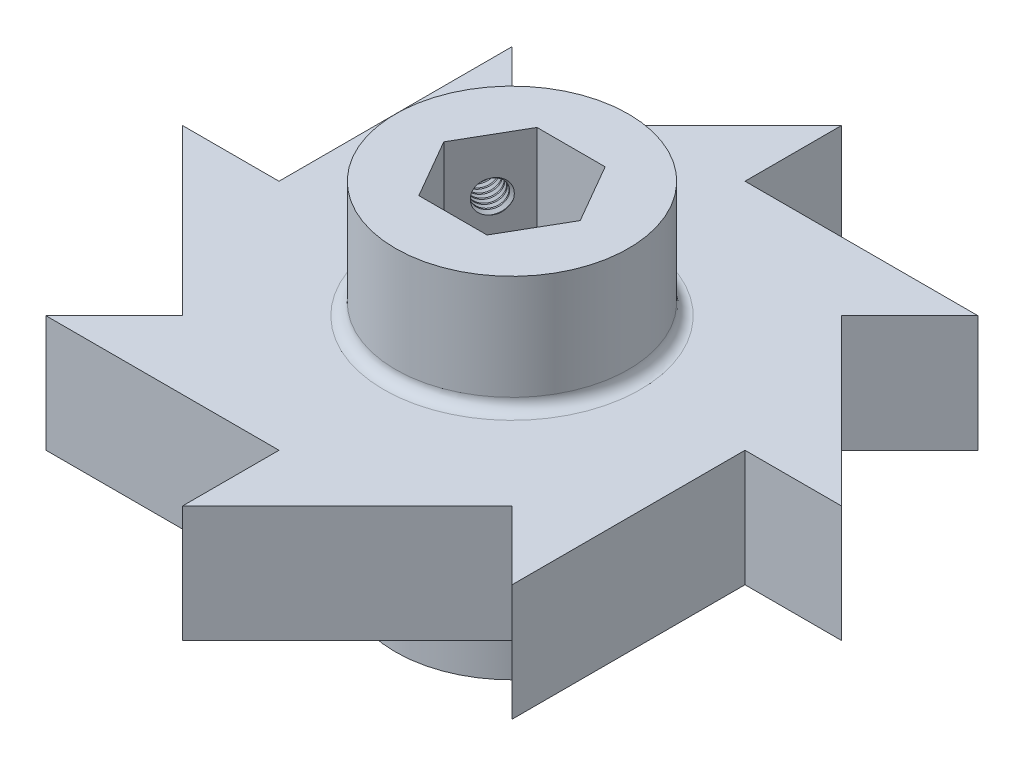
SolidWorks part; units mm, degrees
ref_plane "Front Plane" through (0, 0, 0) normal (0, 0, 1) x (1, 0, 0)
ref_plane "Top Plane" through (0, 0, 0) normal (0, 1, 0) x (1, 0, 0)
ref_plane "Right Plane" through (0, 0, 0) normal (1, 0, 0) x (0, 0, -1)
sketch "Sketch1" plane through (0, 0, 0) normal (0, 1, 0) x (1, 0, 0)
  line L0 (0, 77.6438) -> (0, -76.6604) construction
  line L1 (-67.7775, 0) -> (60.5568, 0) construction
  line L2 (-10.521, 25.4) -> (-17.9605, 17.9605)
  line L3 (-25.4, 10.521) -> (-25.4, 0)
  line L4 (-25.4, -10.521) -> (-17.9605, -17.9605)
  line L5 (-10.521, -25.4) -> (0, -25.4)
  line L6 (10.521, -25.4) -> (17.9605, -17.9605)
  line L7 (25.4, -10.521) -> (25.4, 0)
  line L8 (25.4, 10.521) -> (17.9605, 17.9605)
  line L9 (10.521, 25.4) -> (0, 25.4)
  line L10 (-17.9605, 17.9605) -> (33.7657, -33.7657) construction
  line L11 (17.9605, 17.9605) -> (-25.4, -25.4) construction
  line L12 (-25.4, -10.521) -> (-35.921, 0)
  line L13 (-35.921, 0) -> (-25.4, 0)
  line L15 (-25.4, 10.521) -> (-25.4, 25.4)
  line L16 (-25.4, 25.4) -> (-17.9605, 17.9605)
  line L18 (-10.521, 25.4) -> (0, 35.921)
  line L19 (0, 35.921) -> (0, 25.4)
  line L21 (10.521, 25.4) -> (25.4, 25.4)
  line L22 (25.4, 25.4) -> (17.9605, 17.9605)
  line L24 (25.4, 10.521) -> (35.921, 0)
  line L25 (35.921, 0) -> (25.4, 0)
  line L27 (25.4, -10.521) -> (25.4, -25.4)
  line L28 (25.4, -25.4) -> (17.9605, -17.9605)
  line L30 (10.521, -25.4) -> (0, -35.921)
  line L31 (0, -35.921) -> (0, -25.4)
  line L33 (-10.521, -25.4) -> (-25.4, -25.4)
  line L34 (-25.4, -25.4) -> (-17.9605, -17.9605)
  circle A0 centre (0, 0) radius 25.4 construction
  point P45 (0, 0)
  dimension "D1" = 50.8
  dimension "D4" = 14.879
  dimension "D2" = 8
  dimension "D3" = 10.521
extrude "Boss-Extrude1" add sketch "Sketch1" along normal blind 12.7
sketch "Sketch2" plane through (0, 12.7, 0) normal (0, 1, 0) x (1, 0, 0)
  line L0 (0, 35.921) -> (0, -35.921) construction
  line L1 (-35.921, 0) -> (35.921, 0) construction
  circle A0 centre (0, 0) radius 12.7
  dimension "D1" = 25.4
extrude "Boss-Extrude2" add sketch "Sketch2" along normal blind 12.7 and the other way blind 25.4
fillet "Fillet1" radius 1.27 2 edges at (0, 12.7, 12.7) (0, 0, 12.7)
sketch "Sketch3" plane through (0, 25.4, 0) normal (0, 1, 0) x (1, 0, 0)
  line L0 (0, 25.4) -> (0, 35.921) construction
  line L1 (-3.7175, 6.4389) -> (-7.435, 0)
  line L2 (-7.435, 0) -> (-3.7175, -6.4389)
  line L3 (-3.7175, -6.4389) -> (3.7175, -6.4389)
  line L4 (3.7175, -6.4389) -> (7.435, 0)
  line L5 (7.435, 0) -> (3.7175, 6.4389)
  line L6 (3.7175, 6.4389) -> (-3.7175, 6.4389)
  circle A0 centre (0, 0) radius 6.4389 construction
  dimension "D1" = 12.8778
  dimension "D2" = 90
extrude "Cut-Extrude1" cut sketch "Sketch3" against normal up to surface (38.1 mm away) up to face at (0, -12.7, 12.7)
sketch "Sketch4" plane through (-5.5763, 0, -3.2194) normal (0.866, 0, 0.5) x (0.5, 0, -0.866)
  line L0 (0, 25.4) -> (0, -12.7) construction
  line L1 (12.7, 25.4) -> (-12.7, 25.4) construction
  line L2 (-12.7, -12.7) -> (12.7, -12.7) construction
  line L3 (-12.7, 19.685) -> (12.7, 19.685) construction
  line L4 (-12.7, 25.4) -> (-12.7, 13.97) construction
  line L5 (12.7, 13.97) -> (12.7, 25.4) construction
  line L6 (-12.7, -6.985) -> (12.7, -6.985) construction
  line L7 (-12.7, -1.27) -> (-12.7, -12.7) construction
  line L8 (12.7, -12.7) -> (12.7, -1.27) construction
  circle A0 centre (0, 19.685) radius 1.5875
  circle A1 centre (0, -6.985) radius 1.5875
  dimension "D1" = 3.175
  dimension "D2" = 3.175
extrude "Cut-Extrude2" cut sketch "Sketch4" against normal blind 12.7
thread "Thread2" pitch 0.7 method cut profile "Thread Profile2" start angle 0, offset 2.794, length 10, pitch 0.7, diameter 3.175
ref_plane "Plane2" through (-3.9503, 19.685, -0.4476) normal (0, -1, 0) x (-0.5, 0, 0.866)
sketch "Thread Profile2" plane through (-3.9503, 19.685, -0.4476) normal (0, -1, 0) x (-0.5, 0, 0.866)
  line L0 (0, 0) -> (0, 0.7) construction
  line L1 (0, 0) -> (0.3789, 0.2187)
  line L2 (0.3789, 0.2187) -> (0.3789, 0.3062)
  line L3 (0.3789, 0.3062) -> (0, 0.525)
  line L4 (0.3789, 0.2625) -> (0, 0.2625) construction
  line L11 (0, 0) -> (0, 0.525)
  point P2 (0, 0)
  dimension "Pitch" = 0.7
  dimension "Profile_Angle" = 60
  dimension "Profile_Land" = 0.0875
  dimension "Profile_Height" = 0.3789
thread "Thread3" pitch 0.7 method cut profile "Thread Profile4" start angle 0, offset 2.794, length 10, pitch 0.7, diameter 3.175
ref_plane "Plane4" through (-3.9503, -6.985, -0.4476) normal (0, -1, 0) x (-0.5, 0, 0.866)
sketch "Thread Profile4" plane through (-3.9503, -6.985, -0.4476) normal (0, -1, 0) x (-0.5, 0, 0.866)
  line L0 (0, 0) -> (0, 0.7) construction
  line L1 (0, 0) -> (0.3789, 0.2187)
  line L2 (0.3789, 0.2187) -> (0.3789, 0.3062)
  line L3 (0.3789, 0.3062) -> (0, 0.525)
  line L4 (0.3789, 0.2625) -> (0, 0.2625) construction
  line L11 (0, 0) -> (0, 0.525)
  point P2 (0, 0)
  dimension "Pitch" = 0.7
  dimension "Profile_Angle" = 60
  dimension "Profile_Land" = 0.0875
  dimension "Profile_Height" = 0.3789
